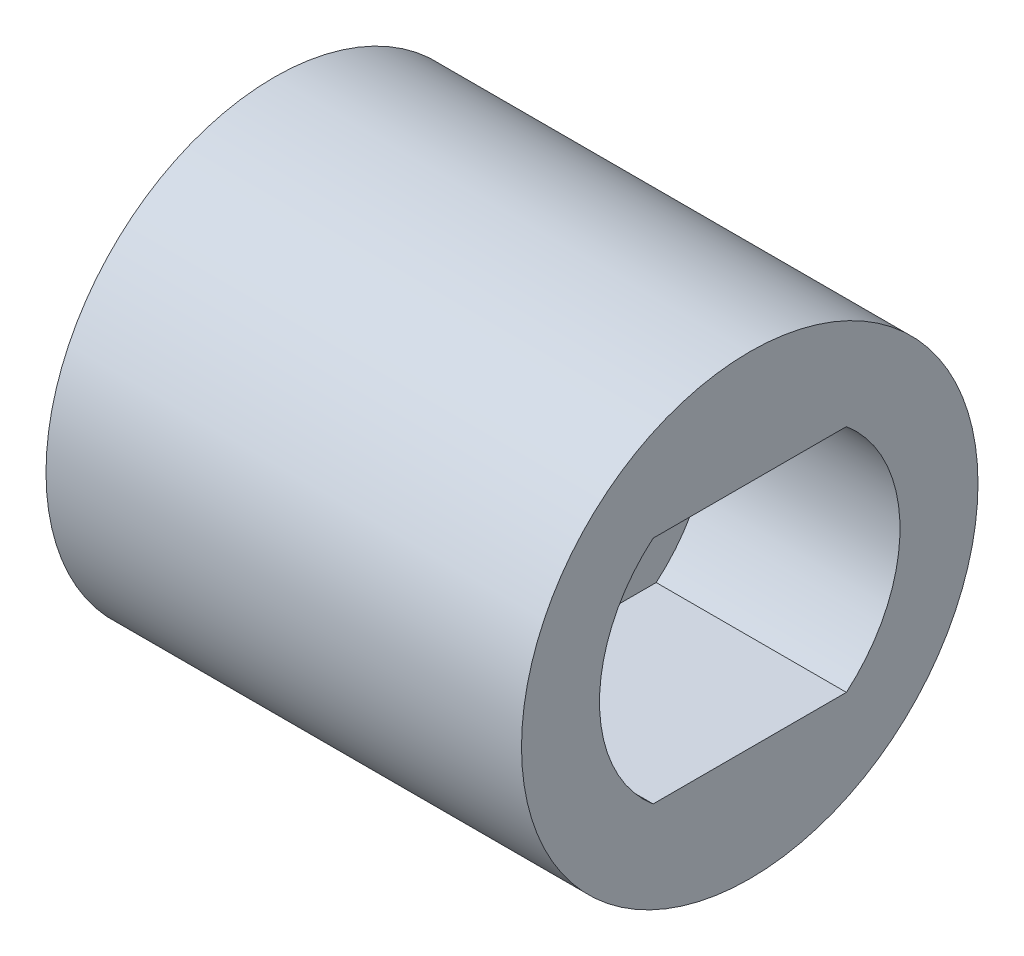
SolidWorks part; units mm, degrees
ref_plane "Plane1" through (0, 0, 0) normal (0, 0, 1) x (1, 0, 0)
ref_plane "Plane2" through (0, 0, 0) normal (0, 1, 0) x (1, 0, 0)
ref_plane "Plane3" through (0, 0, 0) normal (1, 0, 0) x (0, 0, -1)
other "Configuration Table"
sketch "HoldingSke" plane through (0, 0, 0) normal (0, 1, 0) x (1, 0, 0)
  line L0 (0, 0) -> (1.5094, -1.3121)
  line L1 (-15, 0) -> (100, 0) construction
  line L2 (0, 0) -> (-2.1039, 2.3779)
  line L3 (0, 0) -> (-11.863, 4.5341)
  line L4 (0, 0) -> (6.5177, 5.6657)
  line L5 (0, 0) -> (-23.7986, -8.8762)
  line L6 (0, 0) -> (-10.5278, -7.1032)
  line L7 (-2.1039, 2.3779) -> (3.3635, 27.1825)
  line L8 (-76.2, 2.8779) -> (-54.61, 2.8779)
  line L9 (-71.009, 38.7566) -> (-53.1078, 45.2721)
  line L10 (-76.2, 71.12) -> (104.1128, 71.12)
  line L11 (0, 0) -> (-14, 0)
  line L12 (-76.2, 101.6) -> (-76.181, 101.6)
  line L13 (24.9733, 27.94) -> (52.9518, 28.4284)
  line L14 (24.9733, 27.94) -> (24.9743, 27.94)
  line L15 (24.9733, 27.94) -> (100.4006, 29.5858)
  circle A0 centre (0, 0) radius 12
  circle A1 centre (0, 0) radius 12.7
  circle A2 centre (0, 0) radius 12.7
  dimension "Num_teeth" = 41
  dimension "Pitch_radius" = 180.3128
  dimension "Width" = 14
  dimension "Diameter" = 24
sketch "BasProSke" plane through (0, 0, 0) normal (0, 1, 0) x (1, 0, 0)
  line L0 (-10, 0) -> (60, 0) construction
  line L1 (0, 9.75) -> (0, 12)
  line L2 (0, 9.75) -> (14, 9.75)
  line L3 (14, 9.75) -> (14, 12)
  line L4 (14, 12) -> (0, 12)
  dimension "Thickness" = 14
  dimension "Diameter" = 24
revolve "Base-Revolve" add sketch "BasProSke" angle 360 about L0
sketch "TooCutSke" plane through (0, 0, 0) normal (1, 0, 0) x (0, 0, -1)
  line L3 (0.4401, 10.2405) -> (0.4401, 53.6633) construction
  line L4 (0, 0) -> (0, 59.563) construction
  line L5 (0, 0) -> (-5.2304, 68.127) construction
  line L6 (-4.3282, 8.3619) -> (37.0682, 11.5401) construction
  circle A0 centre (0, 0) radius 10.25 construction
  circle A1 centre (0, 0) radius 10.876 construction
  circle A2 centre (0, 0) radius 8.6687 construction
  circle A3 centre (0, 0) radius 9.7246 construction
  arc A4 (0.6177, 9.705) -> (0.1383, 10.8751) centre (-4.3282, 8.3619) ccw
  arc A5 (0.6177, 9.705) -> (-0.6177, 9.705) centre (0, 0) ccw
  arc A6 (0.1383, 10.8751) -> (-0.1383, 10.8751) centre (0, 0) ccw
  arc A7 (-0.1383, 10.8751) -> (-0.6177, 9.705) centre (4.3282, 8.3619) ccw
extrude "ToothCut" cut sketch "TooCutSke" along normal through all
fillet "Breaks" [suppressed] radius 0.05
fillet "RootFillets" [suppressed] radius 0.126
pattern_circular "TeethCuts" count 41 every 8.78 about axis through (-10, 0, 0) along (1, 0, 0) of "RootFillets", "Breaks", "ToothCut"
sketch "草图1" plane through (14, 0, 0) normal (1, 0, 0) x (0, 0, -1)
  line L1 (-7.9, -6.05) -> (7.9, -6.05)
  line L2 (-7.9, -6.05) -> (-7.9, 6.05)
  line L3 (-7.9, 6.05) -> (7.9, 6.05)
  line L4 (7.9, -6.05) -> (7.9, 6.05)
  line L5 (-7.9, -6.05) -> (7.9, 6.05) construction
  line L6 (-7.9, 6.05) -> (7.9, -6.05) construction
  circle A0 centre (0, 0) radius 4
  circle A1 centre (0, 0) radius 7.9
  circle A2 centre (0, 0) radius 12
  point P0 (0, 0)
  dimension "D3" = 8
  dimension "D4" = 24
  dimension "D1" = 15.8
  dimension "D2" = 12.1
extrude "凸台-拉伸1" add sketch "草图1" along normal blind 11 contours A2 A1 L3 L4 L1 L2 | A1 L3 L2 | L3 A1 | A1 L4 L3 | A1 L1 L4 | L1 A1 | A1 L2 L1 | L3 A1 L1 A0 region at (14, -4.5968, 7.0882) region at (14, -3.2534, 6.98) region at (14, -6.798, 0) region at (14, 4.5968, 7.0882) region at (14, -4.5968, -7.0882) region at (14, 6.798, 0) region at (14, 4.5968, -7.0882) region at (14, 0, 11.6606)
extrude "切除-拉伸1" cut sketch "草图1<3>" along normal up to next from offset 1 contours L3 A1 L1 A0 region at (14, -3.2534, 6.98)
sketch "草图1<3>" plane through (14, 0, 0) normal (1, 0, 0) x (0, 0, -1) same geometry as "草图1"
equation "' \"Module@HoldingSke\" = 6.35"
equation "' \"Num_teeth@HoldingSke\" = 24"
equation "' \"Ap@HoldingSke\" =  14.5"
equation "' \"Ap@HoldingSke\" = 14.5"
equation "' \"Width@HoldingSke\" = 12"
equation "' \"Diameter@HoldingSke\" = 8 * 25.4"
equation "' \"Show_teeth@HoldingSke\" = 100"
equation "' \"Backlash@HoldingSke\" = 0.009 * 25.4"
equation "' \"Addendum_fac@HoldingSke\" = 1.0"
equation "' \"Dedendum_fac@HoldingSke\" = 1.25"
equation "' \"Dedendum_add@HoldingSke\" = 0.00005 * 25.4"
equation "' \"Clearance_fac@HoldingSke\" = 0.25"
equation "\"Pitch@HoldingSke\" = 1 / \"Module@HoldingSke\" "
equation "\"Overcut_dia@TooCutSke\" = (\"Num_teeth@HoldingSke\" - 2 * \"Addendum_fac@HoldingSke\") / \"Pitch@HoldingSke\" - 0.002 * 25.4"
equation "\"Pitch_dia@TooCutSke\" = \"Num_teeth@HoldingSke\" / \"Pitch@HoldingSke\""
equation "\"Base_dia@TooCutSke\" = \"Num_teeth@HoldingSke\" / \"Pitch@HoldingSke\" * cos((\"Ap@HoldingSke\"  * 3.14159265 / 180)) * 0.90"
equation "\"Root_dia@TooCutSke\" = \"Num_teeth@HoldingSke\"  / \"Pitch@HoldingSke\" + 2 *  \"Dedendum_fac@HoldingSke\"/ \"Pitch@HoldingSke\" + \"Dedendum_add@HoldingSke\" * 2"
equation "\"Half_ang@TooCutSke\" = 180 / \"Num_teeth@HoldingSke\""
equation "\"Half_CT@TooCutSke\" = \"Num_teeth@HoldingSke\" / \"Pitch@HoldingSke\" * sin((3.14159265 / 2 / \"Num_teeth@HoldingSke\")) / 2 + 10 * \"Backlash@HoldingSke\" / 4"
equation "\"Flank_rad@TooCutSke\" = \"Num_teeth@HoldingSke\" / \"Pitch@HoldingSke\" / 4"
equation "\"Radius@RootFillets\"= \"Clearance_fac@HoldingSke\" / \"Pitch@HoldingSke\" + \"Dedendum_add@HoldingSke\""
equation "\"Break_rad@Breaks\" = 0.02 / \"Pitch@HoldingSke\" * 5"
equation "\"Num_teeth@TeethCuts\" = int( \"Show_teeth@HoldingSke\" ) + 1"
equation "\"Num_teeth@TeethCuts\" = ((sgn( \"Num_teeth@TeethCuts\" - \"Num_teeth@HoldingSke\" )-1)*( \"Num_teeth@TeethCuts\" - \"Num_teeth@HoldingSke\" ))/-2+ \"Num_teeth@HoldingSke\""
equation "\"Num_teeth@TeethCuts\" = ((sgn( \"Num_teeth@TeethCuts\" - 2.0)+1)*( \"Num_teeth@TeethCuts\" - 2.0))/2 +2.0"
equation "\"Angle@TeethCuts\" = 360.0 / \"Num_teeth@HoldingSke\""
equation "\"Diameter@BasProSke\" = \"Num_teeth@HoldingSke\"  / \"Pitch@HoldingSke\" + 2 *  \"Dedendum_fac@HoldingSke\"/ \"Pitch@HoldingSke\" + \"Dedendum_add@HoldingSke\" * 2 + 0.002 * 25.4"
equation "\"Diameter@BasProSke\" = ((sgn( \"Diameter@BasProSke\"  - \"Diameter@HoldingSke\" )+1)*( \"Diameter@BasProSke\"  - \"Diameter@HoldingSke\" ))/2 + \"Diameter@HoldingSke\""
equation "\"Inside_diameter@BasProSke\" =  (\"Num_teeth@HoldingSke\" - 2 * \"Addendum_fac@HoldingSke\") / \"Pitch@HoldingSke\" "
equation "\"Thickness@BasProSke\"  = \"Width@HoldingSke\""
